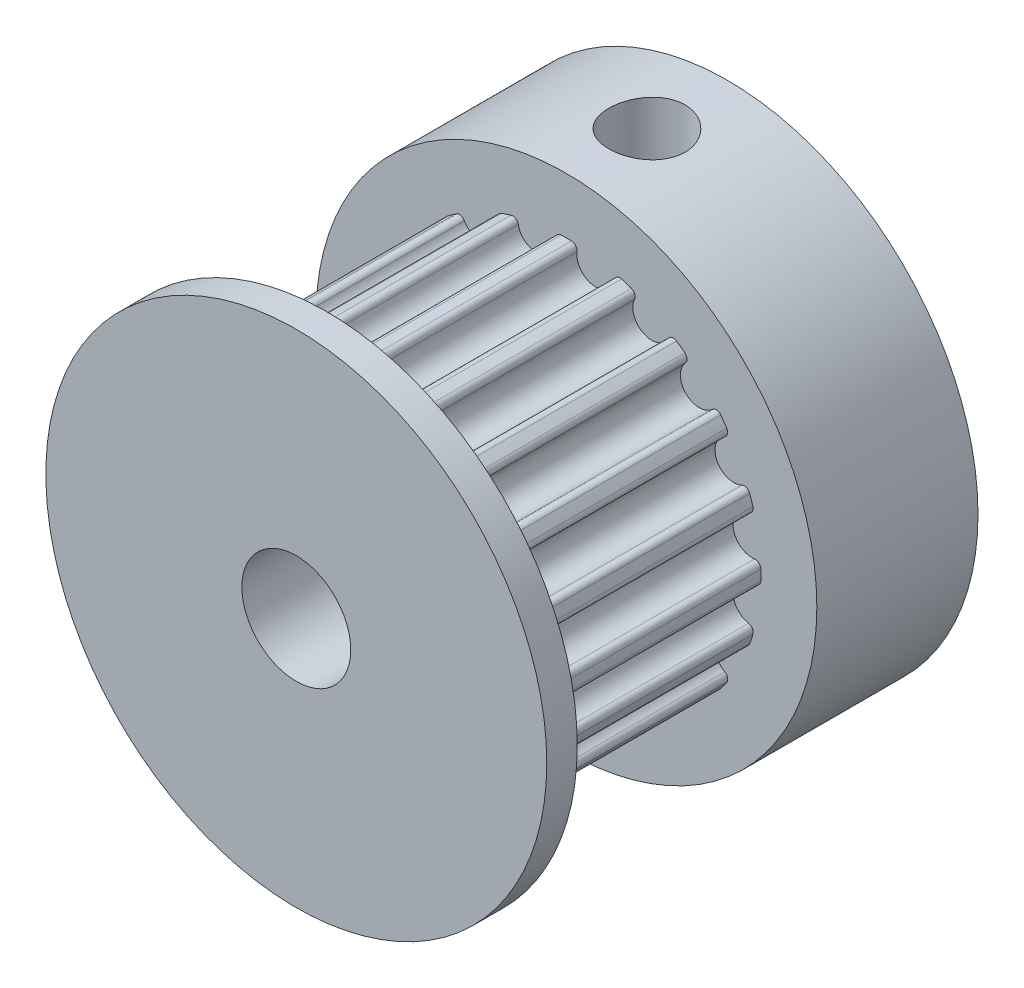
SolidWorks part; units mm, degrees
ref_plane "Front Plane" through (0, 0, 0) normal (1, 0, 0) x (0, 1, 0)
ref_plane "Top Plane" through (0, 0, 0) normal (0, 0, 1) x (0, 1, 0)
ref_plane "Right Plane" through (0, 0, 0) normal (0, 1, 0) x (-1, 0, 0)
other "Configuration Table"
sketch "Sketch2" plane through (0, 0, 0) normal (0, 0, 1) x (0, 1, 0)
  line L0 (0, 0) -> (0, 8.9343)
  line L1 (0, 0) -> (1.2146, 7.6687) construction
  line L2 (1.2146, 7.6687) -> (1.3507, 8.528) construction
  line L3 (0, 0) -> (2.7608, 8.497)
  arc A3 (0.572, 8.916) -> (2.2112, 8.6563) centre (1.3507, 8.528) ccw
  arc A4 (0, 8.9343) -> (0.572, 8.916) centre (0, 0) cw
  arc A5 (2.2112, 8.6563) -> (2.7608, 8.497) centre (0, 0) cw
  dimension "D1" = 8.9343
  dimension "D2" = 7.7643
  dimension "D3" = 9
  dimension "D4" = 0.87
  dimension "D5" = 8.9343
  dimension "D6" = 9
extrude "Boss-Extrude1" add sketch "Sketch2" along normal blind 11 contours A5 A3 A4 L0 L3 region at (-5.4794, 0.8679, 0)
fillet "Fillet2" radius 0.26 2 edges at (-8.6563, 2.2112, 5.5) (-8.916, 0.572, 5.5)
pattern_circular "CirPattern12" count 20 over 360 about axis through (0, 0, 11) along (0, 0, -1) of "Fillet2", "Boss-Extrude1"
sketch "Sketch3" plane through (0, 0, 0) normal (0, 0, 1) x (0, 1, 0)
  circle A0 centre (0, 0) radius 11.5
  circle A1 centre (0, 0) radius 2.5
  dimension "D1" = 23
  dimension "D2" = 5
extrude "Boss-Extrude2" add sketch "Sketch3" against normal blind 7.4 contours A1 | A0 A1 region at (0, -11.1747, 0) region at (0, 0, 0)
extrude "Boss-Extrude3" add sketch "Sketch3<3>" along normal blind 1.4 from surface contours A1 | A0 A1 region at (0, -11.1747, 0) region at (0, 0, 0) starting at face at (0, 0, 11)
sketch "Sketch3<3>" plane through (0, 0, 0) normal (0, 0, 1) x (0, 1, 0) same geometry as "Sketch3"
extrude "Cut-Extrude1" cut sketch "Sketch3<4>" against normal through all both and the other way through all contours A1 region at (0, 0, 0)
sketch "Sketch3<4>" plane through (0, 0, 0) normal (0, 0, 1) x (0, 1, 0) same geometry as "Sketch3"
ref_plane "Plane1" through (-11.5, 0, 0) normal (-1, 0, 0) x (0, 0, 1)
ref_plane "Plane2" through (0, 11.5, 0) normal (0, 1, 0) x (0, 0, 1)
sketch "Sketch4" plane through (-11.5, 0, 0) normal (-1, 0, 0) x (0, 0, 1)
  line L0 (0, -11.5) -> (0, 11.5) construction
  line L1 (0, -11.5) -> (0, 11.5)
  line L2 (-7.4, 11.5) -> (-7.4, -11.5) construction
  line L3 (-7.4, 11.5) -> (-7.4, -11.5)
  line L4 (-7.4, 0) -> (0, 0) construction
  circle A0 centre (-3.7, 0) radius 1.75
  dimension "D1" = 3.5
sketch "Sketch5" plane through (0, 11.5, 0) normal (0, 1, 0) x (0, 0, 1)
  line L0 (0, -11.5) -> (0, 11.5) construction
  line L1 (-7.4, 11.5) -> (-7.4, -11.5) construction
  line L2 (0, -11.5) -> (0, 11.5)
  line L3 (-7.4, 11.5) -> (-7.4, -11.5)
  line L4 (-7.4, 0) -> (0, 0) construction
  circle A0 centre (-3.7, 0) radius 1.75
  dimension "D1" = 3.5
extrude "Cut-Extrude2" cut sketch "Sketch4" against normal up to vertex (11.5 mm away) and the other way through all contours A0 up to point (0, 0, 0)
extrude "Cut-Extrude3" cut sketch "Sketch5" against normal up to vertex (11.5 mm away) contours A0 up to point (0, 0, 0)
equation "\"Pitch\"= 3mm"
equation "\"Teeth\" = 20"
equation "\"Shaft\" = 5mm"
equation "\"BeltHeight\"= 10 + 1"
equation "\"PitchDiameter\"= \"Pitch\" * \"Teeth\" / PI * 1mm"
equation "\"D1@Sketch2\"=\"PitchDiameter\"/2 - 0.615"
equation "\"D2@Sketch2\"=\"D1@Sketch2\"-1.17"
equation "\"D3@Sketch2\"= 180 / \"Teeth\""
equation "\"D1@Boss-Extrude1\"=\"BeltHeight\""
equation "\"D5@Sketch2\"=\"D1@Sketch2\""
equation "\"D6@Sketch2\"=\"D3@Sketch2\""
equation "\"D1@CirPattern12\"=\"Teeth\""
equation "\"Diameter\" = 23"
equation "\"D1@Sketch3\"=\"Diameter\""
equation "\"D2@Sketch3\"=\"Shaft\""
